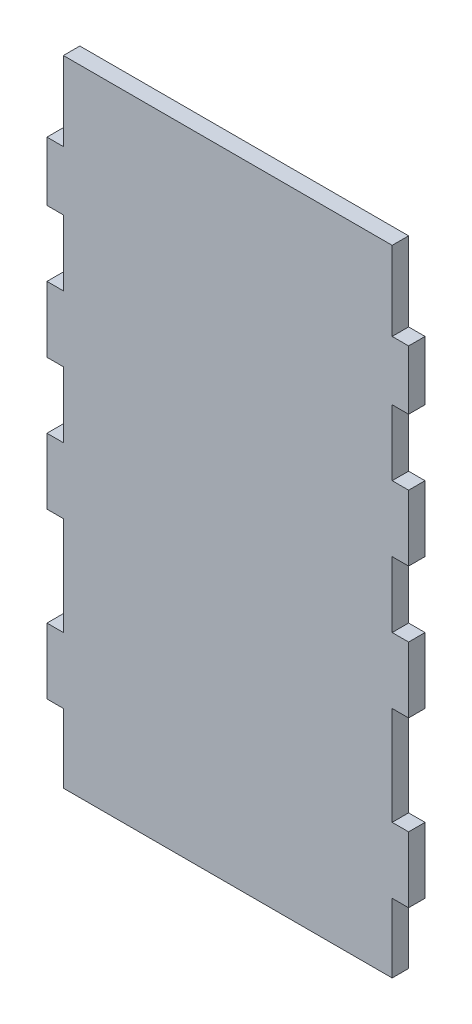
SolidWorks part; units mm, degrees
ref_plane "Front Plane" through (0, 0, 0) normal (0, 0, 1) x (1, 0, 0)
ref_plane "Top Plane" through (0, 0, 0) normal (0, 1, 0) x (1, 0, 0)
ref_plane "Right Plane" through (0, 0, 0) normal (1, 0, 0) x (0, 0, -1)
sketch "Sketch1" plane through (0, 0, 0) normal (0, 0, 1) x (1, 0, 0)
  line L0 (-190.5, 252.73) -> (-209.55, 252.73) construction
  line L1 (6.35, 6.35) -> (-133.35, 6.35)
  line L2 (6.35, 6.35) -> (6.35, 252.73)
  line L3 (6.35, 252.73) -> (-133.35, 252.73)
  line L4 (-133.35, 6.35) -> (-133.35, 252.73)
  line L5 (-127, 1.27) -> (-127, 6.35) construction
  dimension "D1" = 6.35
extrude "Boss-Extrude1" add sketch "Sketch1" along normal blind 6.35
sketch "Sketch2" plane through (6.35, 0, 0) normal (1, 0, 0) x (0, 0, -1)
  line L0 (0, 6.35) -> (0, 252.73) construction
  line L1 (-6.35, 6.35) -> (0, 6.35)
  line L2 (-6.35, 6.35) -> (-6.35, 33.02)
  line L3 (-6.35, 33.02) -> (0, 33.02)
  line L4 (0, 6.35) -> (0, 33.02)
  line L5 (-6.35, 6.35) -> (-6.35, 252.73) construction
  line L6 (-6.35, 58.42) -> (0, 58.42)
  line L7 (-6.35, 58.42) -> (-6.35, 96.52)
  line L8 (-6.35, 96.52) -> (0, 96.52)
  line L9 (0, 58.42) -> (0, 96.52)
  line L11 (-6.35, 121.92) -> (0, 121.92)
  line L12 (-6.35, 121.92) -> (-6.35, 147.32)
  line L13 (-6.35, 147.32) -> (0, 147.32)
  line L14 (0, 121.92) -> (0, 147.32)
  line L15 (-6.35, 172.72) -> (0, 172.72)
  line L16 (-6.35, 172.72) -> (-6.35, 198.12)
  line L17 (-6.35, 198.12) -> (0, 198.12)
  line L18 (0, 172.72) -> (0, 198.12)
  line L19 (0, 220.98) -> (-6.35, 220.98)
  line L20 (0, 220.98) -> (0, 252.73)
  line L21 (0, 252.73) -> (-6.35, 252.73)
  line L22 (-6.35, 220.98) -> (-6.35, 252.73)
  dimension "D1" = 26.67
  dimension "D2" = 25.4
  dimension "D3" = 38.1
  dimension "D4" = 25.4
  dimension "D5" = 25.4
  dimension "D6" = 25.4
  dimension "D7" = 25.4
  dimension "D8" = 22.86
  dimension "D9" = 31.75
extrude "Cut-Extrude1" cut sketch "Sketch2" against normal blind 6.35
sketch "Sketch6" plane through (0, 0, 0) normal (1, 0, 0) x (0, 0, -1)
  line L0 (-6.35, 252.73) -> (-6.35, 220.98) construction
  line L1 (0, 252.73) -> (-6.35, 252.73)
  line L2 (0, 252.73) -> (0, 251.46)
  line L3 (0, 251.46) -> (-6.35, 251.46)
  line L4 (-6.35, 252.73) -> (-6.35, 251.46)
  dimension "D1" = 1.27
sketch "Sketch7" plane through (0, 0, 0) normal (0, 0, -1) x (-1, 0, 0)
  line L0 (66.675, 6.35) -> (66.675, 59.8133) construction
  line L1 (133.35, 6.35) -> (0, 6.35) construction
  line L3 (63.5, 6.35) -> (63.5, 63.249) construction
  line L4 (127, 33.02) -> (127, 6.35)
  line L5 (133.35, 33.02) -> (127, 33.02)
  line L7 (127, 58.42) -> (133.35, 58.42)
  line L8 (127, 96.52) -> (127, 58.42)
  line L9 (133.35, 96.52) -> (127, 96.52)
  line L11 (127, 121.92) -> (133.35, 121.92)
  line L12 (127, 147.32) -> (127, 121.92)
  line L13 (133.35, 147.32) -> (127, 147.32)
  line L15 (127, 172.72) -> (133.35, 172.72)
  line L16 (127, 198.12) -> (127, 172.72)
  line L17 (133.35, 198.12) -> (127, 198.12)
  line L19 (127, 220.98) -> (133.35, 220.98)
  line L20 (127, 247.65) -> (127, 220.98)
  line L21 (127, 247.65) -> (127, 220.98)
  line L22 (127, 33.02) -> (127, 6.35)
  line L23 (127, 96.52) -> (127, 58.42)
  line L24 (127, 147.32) -> (127, 121.92)
  line L25 (127, 198.12) -> (127, 172.72)
  line L26 (127, 247.65) -> (127, 252.73)
  line L27 (0, 252.73) -> (133.35, 252.73) construction
  line L28 (127, 252.73) -> (133.35, 252.73)
  line L29 (133.35, 252.73) -> (133.35, 220.98)
  line L30 (133.35, 6.35) -> (127, 6.35)
  line L31 (133.35, 198.12) -> (133.35, 172.72)
  line L32 (133.35, 147.32) -> (133.35, 121.92)
  line L33 (133.35, 96.52) -> (133.35, 58.42)
  line L34 (133.35, 33.02) -> (133.35, 6.35)
  line M23 (133.35, 6.35) -> (133.35, 252.73)
  line M42 (0, 6.35) -> (133.35, 6.35)
  line M62 (133.35, 252.73) -> (0, 252.73)
  dimension "D2" = 3.175
extrude "Cut-Extrude5" cut sketch "Sketch7" against normal through all contours L5 L4 M23 M42 | L9 L8 L7 M23 | L13 L12 L11 M23 | L17 L16 L15 M23 | L26 L20 L19 M23 M62 region at (-130.175, 19.685, 0) region at (-130.175, 236.855, 0) region at (-130.175, 185.42, 0) region at (-130.175, 134.62, 0) region at (-130.175, 77.47, 0)
sketch "Sketch8" plane through (0, 6.35, 0) normal (0, -1, 0) x (1, 0, 0)
  line L0 (-127, 0) -> (-127, 6.35)
  line L4 (-127, 0) -> (0, 0)
  line L5 (0, 0) -> (0, 6.35)
  line L6 (0, 6.35) -> (-127, 6.35)
  line L7 (-127, 6.35) -> (-127, 0)
  line L8 (-127, 0) -> (0, 0)
  line L9 (0, 0) -> (0, 6.35)
  line L10 (0, 6.35) -> (-127, 6.35)
  line L14 (-127, 6.35) -> (-127, 0)
  dimension "D1" = 0
extrude "Boss-Extrude2" add sketch "Sketch8" along normal blind 3.81 rebuild error yes
extrude "Cut-Extrude6" cut sketch "Sketch6" against normal through all
